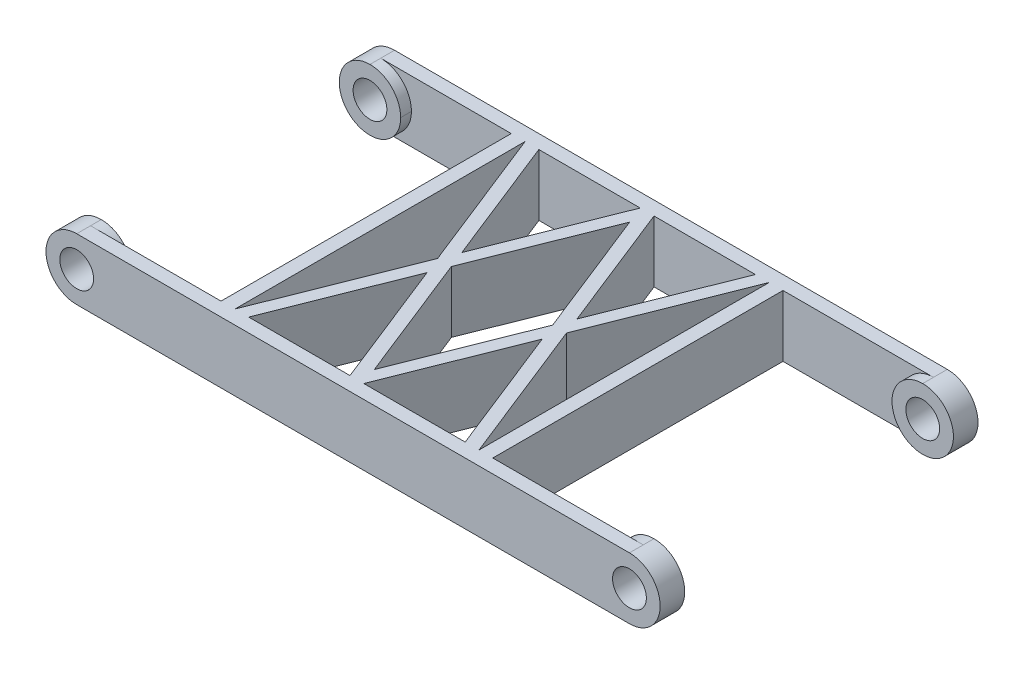
SolidWorks part; units mm, degrees
ref_plane "Front Plane" through (0, 0, 0) normal (0, 0, 1) x (1, 0, 0)
ref_plane "Top Plane" through (0, 0, 0) normal (0, 1, 0) x (1, 0, 0)
ref_plane "Right Plane" through (0, 0, 0) normal (1, 0, 0) x (0, 0, -1)
sketch "Sketch1" plane through (0, 0, 0) normal (0, 0, 1) x (1, 0, 0)
  line L1 (-180, -20) -> (180, -20)
  line L2 (-180, -20) -> (-180, 20) construction
  line L3 (-180, 20) -> (180, 20)
  line L4 (180, -20) -> (180, 20) construction
  line L5 (-180, -20) -> (180, 20) construction
  line L6 (-180, 20) -> (180, -20) construction
  arc A0 (180, -20) -> (180, 20) centre (180, 0) ccw
  arc A1 (-180, -20) -> (-180, 20) centre (-180, 0) cw
  circle A2 centre (-180, 0) radius 11
  circle A3 centre (180, 0) radius 11
  point P0 (0, 0)
  dimension "D3" = 22
  dimension "D1" = 40
  dimension "D2" = 360
extrude "Boss-Extrude1" add sketch "Sketch1" along normal mid plane 207
sketch "Sketch5" plane through (0, 20, 0) normal (0, 1, 0) x (1, 0, 0)
  line L0 (-86, 94.5) -> (-77, 94.5)
  line L1 (-200, 103.5) -> (-160, 103.5)
  line L2 (-200, 103.5) -> (-200, 87.5)
  line L3 (-200, 87.5) -> (-160, 87.5)
  line L4 (-160, 103.5) -> (-160, 87.5)
  line L5 (-200, -103.5) -> (-160, -103.5)
  line L6 (-200, -103.5) -> (-200, -87.5)
  line L7 (-200, -87.5) -> (-160, -87.5)
  line L8 (-160, -103.5) -> (-160, -87.5)
  line L9 (200, -103.5) -> (160, -103.5)
  line L10 (200, -103.5) -> (200, -87.5)
  line L11 (200, -87.5) -> (160, -87.5)
  line L12 (160, -103.5) -> (160, -87.5)
  line L13 (200, 103.5) -> (160, 103.5)
  line L14 (200, 103.5) -> (200, 87.5)
  line L15 (200, 87.5) -> (160, 87.5)
  line L16 (160, 103.5) -> (160, 87.5)
  line L17 (-160, 103.5) -> (160, 103.5)
  line L18 (-160, 103.5) -> (-160, 94.5)
  line L19 (-160, 94.5) -> (160, 94.5)
  line L20 (160, 103.5) -> (160, 94.5)
  line L21 (-160, -103.5) -> (160, -103.5)
  line L22 (-160, -103.5) -> (-160, -94.5)
  line L23 (-160, -94.5) -> (160, -94.5)
  line L24 (160, -103.5) -> (160, -94.5)
  line L25 (-95, 94.5) -> (-86, 94.5)
  line L26 (-95, 94.5) -> (-95, -94.5)
  line L27 (-95, -94.5) -> (-86, -94.5)
  line L28 (-86, 94.5) -> (-86, -94.5)
  line L29 (82, 94.5) -> (73, 94.5)
  line L30 (82, 94.5) -> (82, -94.5)
  line L31 (82, -94.5) -> (73, -94.5)
  line L32 (73, 94.5) -> (73, -94.5)
  line L33 (-86, 94.5) -> (-11, -94.5)
  line L34 (-77, 94.5) -> (-2, -94.5)
  line L35 (-11, -94.5) -> (-2, -94.5)
  line L36 (-11, -94.5) -> (-2, -94.5)
  line L37 (-11, -94.5) -> (64, 94.5)
  line L38 (-2, -94.5) -> (73, 94.5)
  line L39 (64, 94.5) -> (73, 94.5)
  line L48 (-86, -94.5) -> (-77, -94.5)
  line L49 (-86, -94.5) -> (-11, 94.5)
  line L50 (-77, -94.5) -> (-2, 94.5)
  line L51 (-11, 94.5) -> (-2, 94.5)
  line L52 (-11, 94.5) -> (-2, 94.5)
  line L53 (-11, 94.5) -> (64, -94.5)
  line L54 (-2, 94.5) -> (73, -94.5)
  line L55 (64, -94.5) -> (73, -94.5)
  line L57 (-200, 87.5) -> (-200, -87.5)
  line L58 (200, 87.5) -> (200, -87.5)
  line M14 (-180, 103.5) -> (-180, -103.5)
  line M16 (180, -103.5) -> (180, 103.5)
  dimension "D1" = 16
  dimension "D2" = 9
  dimension "D3" = 40
  dimension "D4" = 105
  dimension "D5" = 118
extrude "Cut-Extrude1" cut sketch "Sketch5" against normal up to surface (40 mm away) contours L26 L19 L4 L3 L7 L8 L23 M14 | L3 L57 L7 M14 | L28 L49 L33 | L34 L49 L19 | L53 L50 L34 L37 | L50 L23 L33 | L19 L54 L37 | L38 L54 L32 | L53 L38 L23 | L19 L30 L23 L12 L11 L15 L16 M16 | L58 L15 L11 M16 region at (-73.5, 20, 0) region at (-44, 20, -66.78) region at (-136.9235, 20, 0) region at (-44, 20, 66.78) region at (31, 20, -66.78) region at (-6.5, 20, 0) region at (-190, 20, 0) region at (31, 20, 66.78) region at (60.5, 20, 0) region at (130.4014, 20, 0) region at (190, 20, 0) up to face at (0, -20, 0)
fillet "Fillet1" radius 20 8 edges at (160, -20, 91) (160, 20, 91) (160, -20, -91) (160, 20, -91) (-160, -20, 91) (-160, 20, 91) (-160, -20, -91) (-160, 20, -91)
